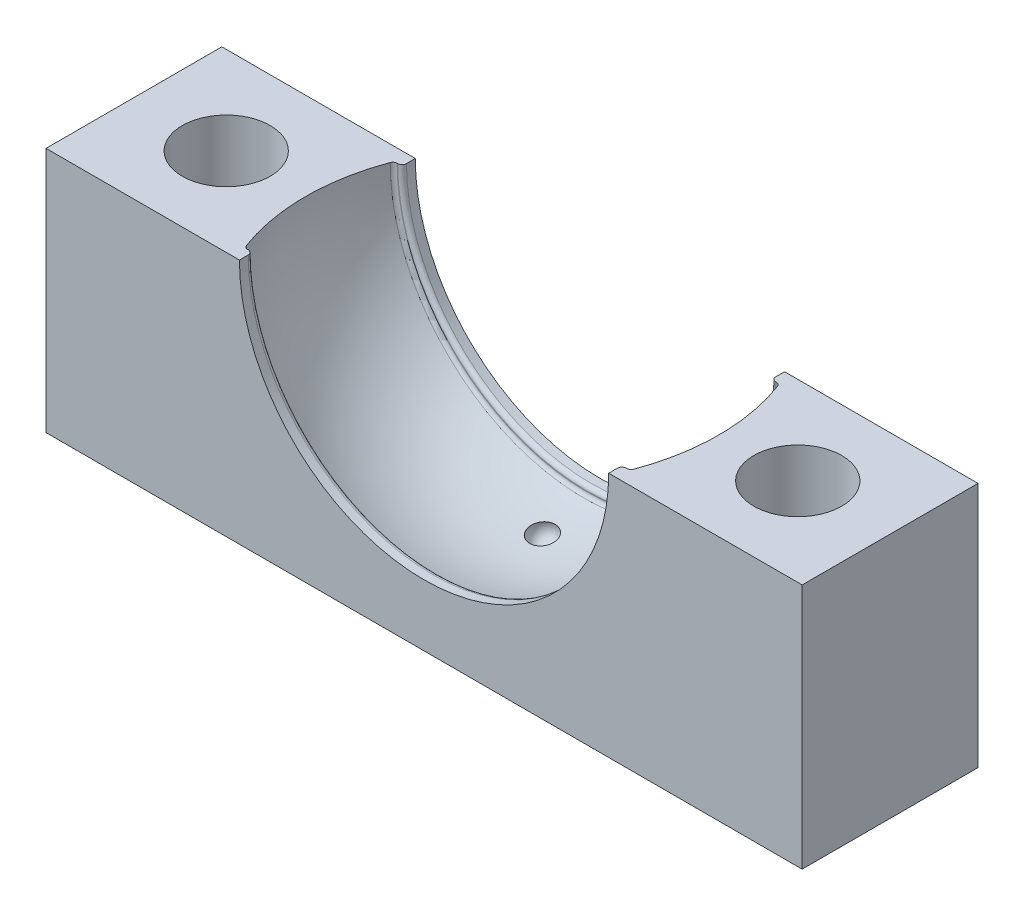
SolidWorks part; units mm, degrees
ref_plane "Front Plane" through (0, 0, 0) normal (0, 0, 1) x (1, 0, 0)
ref_plane "Top Plane" through (0, 0, 0) normal (0, 1, 0) x (1, 0, 0)
ref_plane "Right Plane" through (0, 0, 0) normal (1, 0, 0) x (0, 0, -1)
sketch "Sketch1" plane through (0, 0, 0) normal (0, 0, 1) x (1, 0, 0)
  line L0 (0, 0) -> (0, 79.999) construction
  line L1 (43, 0) -> (-43, 0)
  line L2 (-43, 0) -> (-43, 28)
  line L5 (43, 0) -> (43, 28)
  line L10 (-43, 28) -> (43, 28)
  dimension "D2" = 43
  dimension "D3" = 28
extrude "Boss-Extrude1" add sketch "Sketch1" along normal blind 20
sketch "Sketch2" plane through (0, 0, 0) normal (0, 1, 0) x (1, 0, 0)
  line L1 (-43, -20) -> (-43, 0) construction
  line L2 (-23, -20) -> (-40, -20) construction
  line L3 (0, 0) -> (0, -21.8102) construction
  circle A0 centre (-32.5, -10) radius 5
  circle A1 centre (32.5, -10) radius 5
  point P12 (-43, -10)
  dimension "D1" = 10
  dimension "D2" = 32.5
  dimension "D3" = 10
extrude "Cut-Extrude1" cut sketch "Sketch2" along normal through all
sketch "Sketch4" plane through (0, 28, 0) normal (0, 1, 0) x (-1, 0, 0)
  line L17 (0, 0) -> (0, 20) construction
  line L20 (0, 0) -> (0, 20)
  line L21 (0, 0) -> (21, 0)
  line L22 (0, 20) -> (21, 20)
  line L23 (21, 0) -> (21, 1.5)
  line L24 (21, 1.5) -> (21.9089, 1.5)
  line L25 (0, 10) -> (41.3238, 10) construction
  line L26 (21, 20) -> (21, 18.5)
  line L27 (21, 18.5) -> (21.9089, 18.5)
  arc A2 (21.9089, 18.5) -> (21.9089, 1.5) centre (0, 10) cw
  point P6 (0, 10)
  point P7 (0, 10)
  dimension "D2" = 23.5
  dimension "D1" = 20
  dimension "D3" = 1.5
  dimension "D4" = 21
revolve "Cut-Revolve1" cut sketch "Sketch4" angle 360 about L20
ref_plane "Plane1" through (0, 4.5, 0) normal (0, 1, 0) x (1, 0, 0)
sketch "Sketch5" plane through (0, 4.5, 0) normal (0, 1, 0) x (1, 0, 0)
  line L0 (0, 0) -> (0, -42.728) construction
  line L1 (-21, -1.5) -> (21, -1.5) construction
  line L2 (0, -5) -> (0, -8)
  arc A0 (0, -5) -> (0, -8) centre (0, -6.5) ccw
  point P3 (0, -6.5)
  dimension "D2" = 1.5
  dimension "D1" = 5
revolve "Cut-Revolve2" cut sketch "Sketch5" angle 360 about L0
fillet "Fillet1" radius 0.5 2 edges at (0, 6.0911, 1.5) (0, 6.0911, 18.5)
fillet "Fillet2" radius 0.5 2 edges at (0, 7, 18.5) (0, 7, 1.5)
